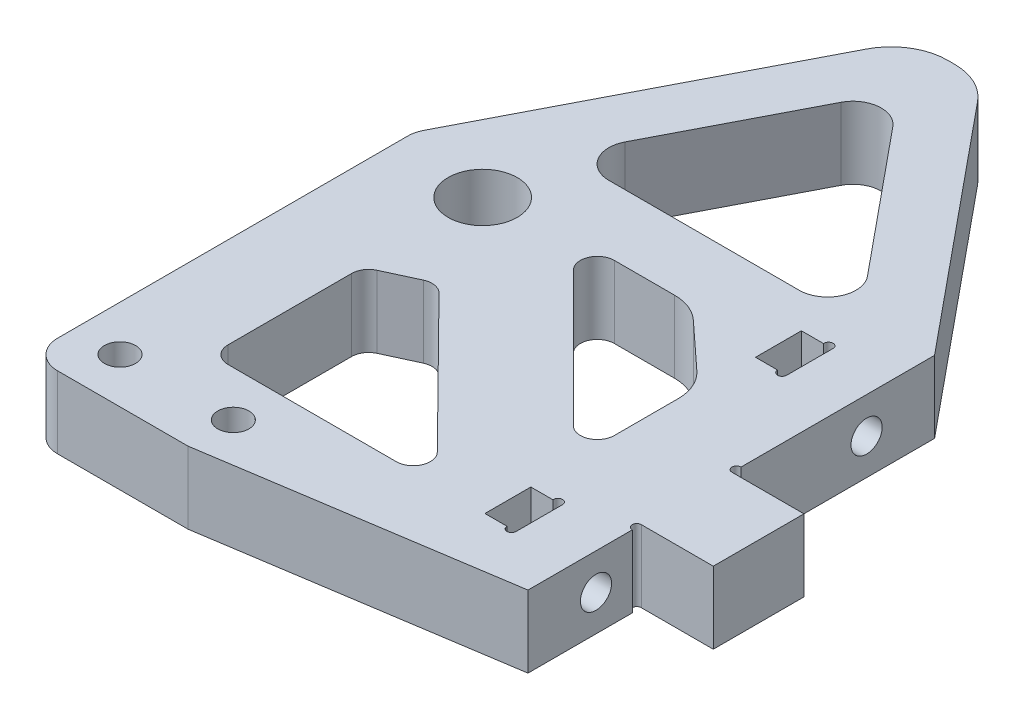
SolidWorks part; units mm, degrees
material "6061 Alloy"
ref_plane "Front Plane" through (0, 0, 0) normal (0, 0, 1) x (1, 0, 0)
ref_plane "Top Plane" through (0, 0, 0) normal (0, 1, 0) x (1, 0, 0)
ref_plane "Right Plane" through (0, 0, 0) normal (1, 0, 0) x (0, 0, -1)
sketch "Sketch1" plane through (0, 0, 0) normal (0, 1, 0) x (1, 0, 0)
  line L1 (-80, 0) -> (-80, 60)
  line L7 (0, 0) -> (-52, -8)
  line L8 (-52, -8) -> (-80, -8)
  line L9 (-80, -8) -> (-80, 0)
  line L10 (-80, 60) -> (-50, 118)
  line L11 (-50, 118) -> (-38, 118)
  line L12 (-38, 118) -> (0, 71.75)
  line L14 (0, 36) -> (12.7, 36)
  line L15 (12.7, 36) -> (12.7, 20)
  line L16 (12.7, 20) -> (0, 20)
  line L18 (0, 18.4) -> (0, 0)
  line L19 (0, 71.75) -> (0, 37.6)
  circle A0 centre (-64, 56) radius 6.1
  circle A3 centre (-72, 0) radius 2.75
  circle A4 centre (-52, 0) radius 2.75
  arc A5 (0, 20) -> (0, 18.4) centre (0, 19.2) ccw
  arc A6 (0, 36) -> (0, 37.6) centre (0, 36.8) cw
  point P23 (12.7, 28)
  dimension "D8" = 12.2
  dimension "D12" = 5.5
  dimension "D16" = 5.5
  dimension "D19" = 0.8
  dimension "D20" = 0.8
  dimension "D1" = 80
  dimension "D2" = 71.75
  dimension "D3" = 60
  dimension "D9" = 16
  dimension "D14" = 8
  dimension "D15" = 20
  dimension "D10" = 8
  dimension "D13" = 8
  dimension "D17" = 56
  dimension "D4" = 58
  dimension "D5" = 30
  dimension "D6" = 12
  dimension "D18" = 12.7
  dimension "D7" = 28
  dimension "D11" = 16
extrude "Boss-Extrude1" add sketch "Sketch1" along normal blind 12.7
fillet "Fillet1" radius 10 2 edges at (-38, 6.35, -118) (-50, 6.35, -118)
sketch "Sketch3" plane through (0, 12.7, 0) normal (0, 1, 0) x (1, 0, 0)
  line L5 (-11.2992, 69.75) -> (-43.4551, 108.8871)
  line L6 (-43.4551, 108.8871) -> (-63.6984, 69.75)
  line L7 (-63.6984, 69.75) -> (-11.2992, 69.75)
  line L10 (0, 71.75) -> (-34.9997, 114.3483) construction
  line L11 (-52.7961, 112.5942) -> (-80, 60) construction
  line L12 (-29.1082, 13.1082) -> (-54.7017, 39.0201)
  line L16 (-80, 60) -> (-80, -8) construction
  line L17 (-63.9447, 34.7442) -> (-63.9447, 8)
  line L18 (-54.7017, 39.0201) -> (-63.9447, 34.7442)
  line L19 (-63.9447, 8) -> (-31.2426, 8)
  line L20 (-42.7574, 58) -> (-32.1279, 58)
  line L21 (-26.7016, 55.8784) -> (-18.5738, 48.3758)
  line L22 (-16, 42.4974) -> (-16, 31.2426)
  line L23 (-21.1213, 29.1213) -> (-44.8787, 52.8787)
  arc A3 (-31.2426, 8) -> (-29.1082, 13.1082) centre (-31.2426, 11) ccw
  arc A4 (-21.1213, 29.1213) -> (-16, 31.2426) centre (-19, 31.2426) ccw
  arc A5 (-44.8787, 52.8787) -> (-42.7574, 58) centre (-42.7574, 55) cw
  arc A6 (-16, 42.4974) -> (-18.5738, 48.3758) centre (-24, 42.4974) ccw
  arc A7 (-26.7016, 55.8784) -> (-32.1279, 58) centre (-32.1279, 50) ccw
  point P19 (-16, 24)
  point P21 (-16, 58)
  point P23 (-50, 58)
  point P24 (-50, 58)
  point P27 (-16, 24)
  point P30 (-24, 8)
  point P31 (-16, 46)
  point P34 (-29, 58)
  point P36 (-58, 42)
  dimension "D8" = 3
  dimension "D9" = 8
  dimension "D1" = 10
  dimension "D2" = 10
  dimension "D3" = 10
  dimension "D4" = 10
  dimension "D5" = 2
  dimension "D6" = 22
  dimension "D7" = 13
  dimension "D10" = 64
  dimension "D11" = 32
  dimension "D12" = 34
  dimension "D13" = 34
extrude "Cut-Extrude1" cut sketch "Sketch3" against normal through all
fillet "Fillet2" radius 5 3 edges at (-43.4551, 6.35, -108.8871) (-11.2992, 6.35, -69.75) (-63.6984, 6.35, -69.75)
sketch "Sketch4" plane through (0, 12.7, 0) normal (0, 1, 0) x (1, 0, 0)
  line L0 (0, 0) -> (0, 18.4) construction
  line L2 (-15.5, 16) -> (-15.5, 7.9)
  line L4 (-10, 16.1) -> (-10, 7.9)
  line L5 (-15.5, 16) -> (-11.5937, 16)
  line L6 (-15.5, 7.9) -> (-11.6, 7.9)
  line L7 (-15.5, 55.65) -> (-11.6, 55.65)
  line L8 (-10, 63.85) -> (-10, 55.65)
  line L9 (-15.5, 63.75) -> (-11.5937, 63.75)
  line L10 (-15.5, 63.75) -> (-15.5, 55.65)
  arc A0 (-10, 16.1) -> (-11.5937, 16) centre (-10.8, 16.1) ccw
  arc A1 (-10, 7.9) -> (-11.6, 7.9) centre (-10.8, 7.9) cw
  arc A2 (-10, 55.65) -> (-11.6, 55.65) centre (-10.8, 55.65) cw
  arc A3 (-10, 63.85) -> (-11.5937, 63.75) centre (-10.8, 63.85) ccw
  point P4 (-10, 12)
  point P12 (-10, 59.75)
  dimension "D5" = 0.8
  dimension "D1" = 12
  dimension "D2" = 10
  dimension "D3" = 8.2
  dimension "D4" = 5.5
  dimension "D7" = 12
  dimension "D6" = 2
extrude "Cut-Extrude2" cut sketch "Sketch4" against normal through all
sketch "Sketch6" plane through (-10, 0, 0) normal (-1, 0, 0) x (0, 0, 1)
  line L0 (-7.9, 0) -> (-7.9, 12.7) construction
  line L1 (-7.9, 12.7) -> (-16.1, 12.7) construction
  line L2 (-55.65, 0) -> (-55.65, 12.7) construction
  circle A0 centre (-12, 6.35) radius 2.75
  circle A1 centre (-59.75, 6.35) radius 2.75
  dimension "D2" = 5.5
  dimension "D5" = 5.5
  dimension "D1" = 4.1
  dimension "D3" = 6.35
  dimension "D4" = 4.1
extrude "Cut-Extrude3" cut sketch "Sketch6" against normal through all
fillet "Fillet3" radius 3 3 edges at (-54.7017, 6.35, -39.0201) (-63.9447, 6.35, -8) (-63.9447, 6.35, -34.7442)
fillet "Fillet4" radius 5 2 edges at (-80, 6.35, 8) (-80, 6.35, -60)
equation "\"DriveMotorLength\"= 90mm"
equation "\"DriveMotorGap\"= 10mm"
equation "\"AluminumThickness\"= 0.5in"
equation "\"ChassisWidth\"= ( \"DriveMotorLength\" + \"AluminumThickness\" ) * 2 + \"DriveMotorGap\""
equation "\"RepeatMagnumHoleWidth\"= 19.05mm"
equation "\"MortiseWidth\"= 16mm"
equation "\"ChassisScrewThruHole\"= 5.5mm"
equation "\"D12@Sketch1\"=\"ChassisScrewThruHole\""
equation "\"D16@Sketch1\"=\"ChassisScrewThruHole\""
equation "\"MortiseSlotWidth\"= 16.2mm"
equation "\"Dogbone\"= 0.8mm"
equation "\"D19@Sketch1\"=\"Dogbone\""
equation "\"D20@Sketch1\"=\"Dogbone\""
equation "\"D5@Sketch4\"=\"Dogbone\""
equation "\"D2@Sketch6\"=\"ChassisScrewThruHole\""
equation "\"D5@Sketch6\"=\"ChassisScrewThruHole\""
equation "\"D11@Sketch1\"=\"MortiseWidth\""
